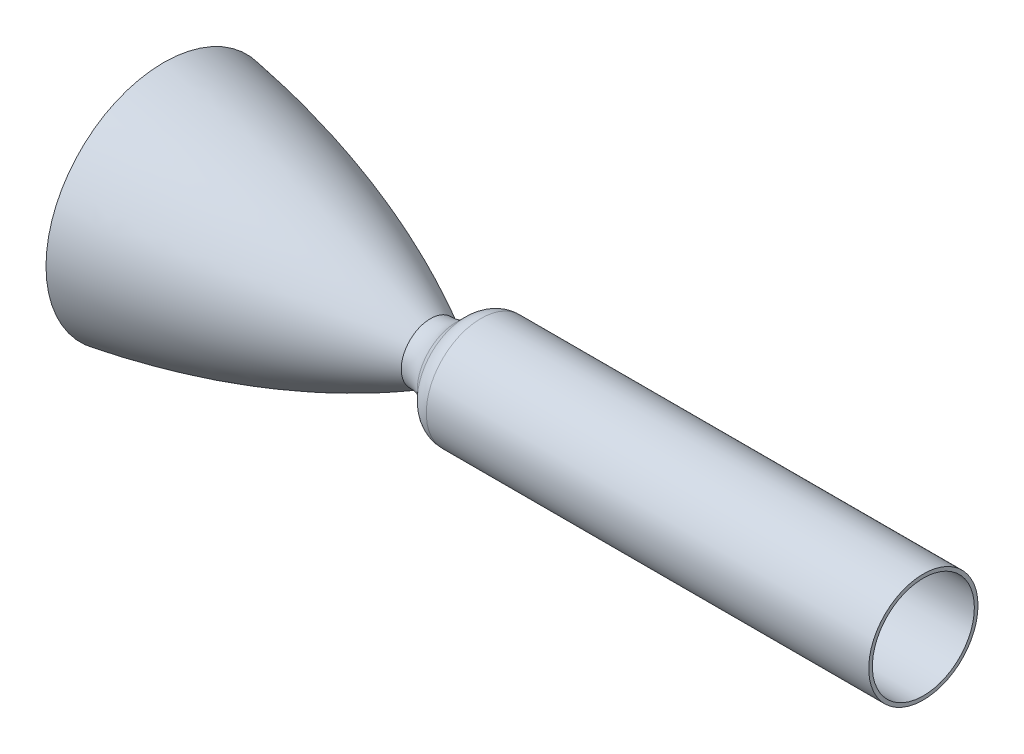
SolidWorks part; units mm, degrees
ref_plane "Front Plane" through (0, 0, 0) normal (0, 0, 1) x (1, 0, 0)
ref_plane "Top Plane" through (0, 0, 0) normal (0, 1, 0) x (1, 0, 0)
ref_plane "Right Plane" through (0, 0, 0) normal (1, 0, 0) x (0, 0, -1)
sketch "Sketch1" plane through (0, 0, 0) normal (0, 0, 1) x (1, 0, 0)
  line L0 (272.3324, 28) -> (29.4035, 28)
  line L1 (22.3324, 25.0711) -> (17.4121, 20.1508)
  line L3 (0, 0) -> (-234.9488, 0) construction
  line L8 (272.3324, 30) -> (29.4035, 30)
  line L12 (20.9182, 26.4853) -> (15.9979, 21.565)
  line L13 (272.3324, 28) -> (272.3324, 30)
  line L14 (-145.1317, 62.6099) -> (-144.8157, 64.5848)
  arc A0 (29.4035, 28) -> (22.3324, 25.0711) centre (29.4035, 18) ccw
  arc A4 (29.4035, 30) -> (20.9182, 26.4853) centre (29.4035, 18) ccw
  arc A7 (1.67, 16.021) -> (1.67, 16.021) centre (1.67, 16.021) cw
  arc A8 (15.9979, 21.565) -> (1.67, 16.021) centre (2.5629, 35) cw construction
  arc A9 (1.67, 16.021) -> (15.9979, 21.565) centre (2.5629, 35) ccw
  arc A10 (-0.2556, 14.19) -> (0, 14.6541) centre (2.9733, 12.7139) cw construction
  arc A11 (17.4121, 20.1508) -> (-0.2556, 14.19) centre (2.5629, 35) cw construction
  arc A12 (17.4121, 20.1508) -> (2.5629, 14) centre (2.5629, 35) cw
  arc A13 (2.5629, 14) -> (0, 14.6541) centre (2.5629, 19.348) cw
  spline S0 degree 2 poles (0, 14.6541) (-64.0809, 49.6422) (-145.1317, 62.6099) knots 0 0 0 1 1 1 construction
  spline S1 degree 1 poles (1.67, 16.021) (-144.8157, 64.5848) knots 0 0 1 1 construction
  spline S2 degree 2 poles (0, 14.6541) (-64.0809, 49.6422) (-145.1317, 62.6099) knots 0 0 0 1 1 1
  spline S3 degree 2 poles (1.67, 16.021) (-63.0098, 51.5015) (-144.8157, 64.5848) knots -0.005552 -0.005552 -0.005552 1 1 1
  point P15 (3.9695, 9.6565)
  point P16 (0, 0)
  point P17 (3.6494, 36.4325)
  point P25 (2.1845, 37.8974)
  dimension "D1" = 10
  dimension "D4" = 21
  dimension "D5" = 5.348
  dimension "D14" = 28
  dimension "D16" = 250
  dimension "D2" = 14
  dimension "D6" = 45
  dimension "D7" = 62.6099
  dimension "D3" = 2
revolve "Revolve1" add sketch "Sketch1" angle 360 about L3 region at (150.868, 28.4205, 0)
equation "\"theta_t\"= 36.9009 - ( 426.271 / ( \"Aet\" + 7.00037 ) ) + ( 10026.8 / ( \"Aet\" + 7.00037 ) ^ 2 ) - ( 175410 / ( \"Aet\" + 7.00037 ) ^ 3 ) + ( ( 1.6742 * ( 10 ^ 6 ) ) / ( \"Aet\" + 7.00037 ) ^ 4 ) - ( ( 6.7643 * ( 10 ^ 6 ) ) / ( \"Aet\" + 7.00037 ) ^ 5 )"
equation "\"rt\"= 14"
equation "\"re\"= sqr ( \"rt\" ^ 2 * \"Aet\" )"
equation "\"Aet\"= 20"
equation "\"L\"= 0.8 * ( ( \"re\" / tan ( 15 ) ) - ( \"rt\" / tan ( 15 ) ) )"
equation "\"lc\"= ( \"l*\" / \"cr\" )"
equation "\"b\"= tan ( \"theta_t\" )"
equation "\"a\"= ( \"re\" - \"b\" * \"L\" - \"c\" ) / \"L\" ^ 2"
equation "\"c\"= \"rt\" * ( 1.382 - 0.382 * cos ( \"theta_t\" ) )"
equation "\"cr\"= 4"
equation "\"rc\"= sqr ( \"cr\" * ( \"rt\" ^ 2 ) )"
equation "\"D14@Sketch1\"=\"rc\""
equation "\"l*\"= 1000"
equation "\"D16@Sketch1\"=\"lc\""
equation "\"th\"= 2"
equation "\"theta_cr\"= 45deg"
equation "\"theta_e\"= 5.48 + ( 134.316 / ( \"Aet\" + 1.49269 ) ) - ( 1742.02 / ( \"Aet\" + 1.49269 ) ^ 2 ) + ( 13091 / ( \"Aet\" + 1.49269 ) ^ 3 ) - ( 41929.9 / ( \"Aet\" + 1.49269 ) ^ 4 ) + ( 44445.1 / ( \"Aet\" + 1.49269 ) ^ 5 )"
equation "\"Nx\"= 0"
equation "\"Ny\"= \"c\""
equation "\"Qx\"= ( \"re\" - ( tan ( \"theta_e\" ) * \"L\" ) - \"c\" ) / ( tan ( \"theta_t\" ) - tan ( \"theta_e\" ) )"
equation "\"Qy\"= tan ( \"theta_t\" ) * \"Qx\" + \"c\""
equation "\"Ex\"= \"L\""
equation "\"Ey\"= \"re\""
equation "\"D3@Sketch1\"=\"th\""
equation "\"D2@Sketch1\"=\"rt\""
equation "\"D4@Sketch1\"=\"rt\"*1.5"
equation "\"D5@Sketch1\"=\"rt\"*0.382"
equation "\"D6@Sketch1\"=\"theta_cr\""
equation "\"D7@Sketch1\"=\"re\""
